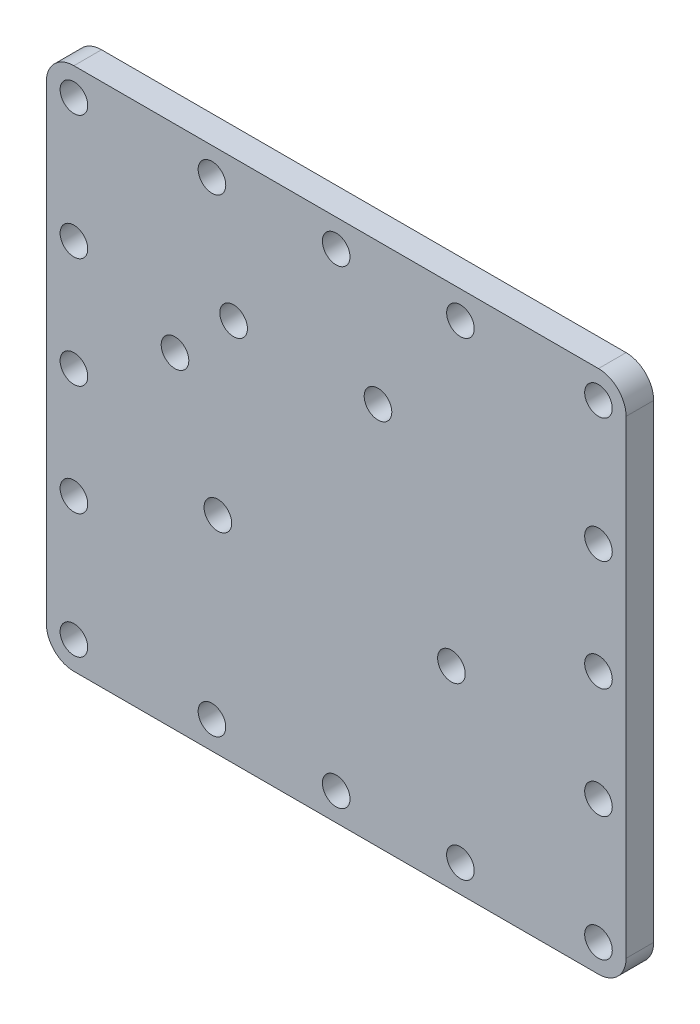
SolidWorks part; units mm, degrees
ref_plane "前视基准面" through (0, 0, 0) normal (0, 0, 1) x (1, 0, 0)
ref_plane "上视基准面" through (0, 0, 0) normal (0, 1, 0) x (1, 0, 0)
ref_plane "右视基准面" through (0, 0, 0) normal (1, 0, 0) x (0, 0, -1)
sketch "草图1" plane through (0, 0, 0) normal (0, 0, 1) x (1, 0, 0)
  line L0 (0, 41.5424) -> (0, -51.1772) construction
  line L1 (-95, -95) -> (95, -95)
  line L2 (-105, -85) -> (-105, 85)
  line L3 (-95, 95) -> (95, 95)
  line L4 (105, -85) -> (105, 85)
  line L5 (-105, -95) -> (105, 95) construction
  line L6 (-105, 95) -> (99.7638, -90.2625) construction
  line L7 (-39.3089, 0) -> (48.7848, 0) construction
  line L8 (95, 85) -> (95, -85) construction
  line L9 (-95, 85) -> (95, 85) construction
  circle A0 centre (-95, 85) radius 5
  circle A1 centre (95, 85) radius 5
  circle A2 centre (95, -85) radius 5
  circle A3 centre (-95, -85) radius 5
  arc A4 (95, 95) -> (105, 85) centre (95, 85) cw
  arc A5 (95, -95) -> (105, -85) centre (95, -85) ccw
  arc A6 (-95, -95) -> (-105, -85) centre (-95, -85) cw
  arc A7 (-105, 85) -> (-95, 95) centre (-95, 85) cw
  circle A8 centre (-37.156, 43.9209) radius 5
  circle A9 centre (15.1451, 43.9209) radius 5
  circle A10 centre (-58.3861, 23.2709) radius 5
  circle A11 centre (-42.8628, -19.9411) radius 5
  circle A12 centre (41.7332, -24.9411) radius 5
  circle A13 centre (95, 0) radius 5
  circle A14 centre (95, 40) radius 5
  circle A15 centre (95, -40) radius 5
  circle A16 centre (-95, -40) radius 5
  circle A17 centre (-95, 0) radius 5
  circle A18 centre (-95, 40) radius 5
  circle A19 centre (0, 85) radius 5
  circle A20 centre (-45, 85) radius 5
  circle A21 centre (45, 85) radius 5
  circle A22 centre (45, -85) radius 5
  circle A23 centre (0, -85) radius 5
  circle A24 centre (-45, -85) radius 5
  point P0 (0, 0)
  dimension "D2" = 10
  dimension "D3" = 10
  dimension "D4" = 10
  dimension "D6" = 10
  dimension "D7" = 10
  dimension "D8" = 10
  dimension "D9" = 10
  dimension "D10" = 10
  dimension "D11" = 10
  dimension "D12" = 10
  dimension "D13" = 10
  dimension "D14" = 40
  dimension "D15" = 40
  dimension "D16" = 10
  dimension "D17" = 10
  dimension "D18" = 45
  dimension "D19" = 45
  dimension "D1" = 190
  dimension "D5" = 210
extrude "凸台-拉伸1" add sketch "草图1" along normal mid plane 10
sketch "草图2" plane through (0, 0, -5) normal (0, 0, -1) x (-1, 0, 0)
  line L1 (-67.5, -62.5) -> (67.5, -62.5)
  line L2 (-67.5, -62.5) -> (-67.5, 62.5)
  line L3 (-67.5, 62.5) -> (67.5, 62.5)
  line L4 (67.5, -62.5) -> (67.5, 62.5)
  line L5 (-67.5, -62.5) -> (67.5, 62.5) construction
  line L6 (-67.5, 62.5) -> (67.5, -62.5) construction
  point P0 (0, 0)
  dimension "D1" = 135
  dimension "D2" = 125
extrude "切除-拉伸1" cut sketch "草图2" against normal blind 1
sketch "草图3" plane through (0, 0, -5) normal (0, 0, -1) x (-1, 0, 0)
  line L1 (-67.5, -65) -> (67.5, -65)
  line L2 (-72.5, -60) -> (-72.5, 60)
  line L3 (-67.5, 65) -> (67.5, 65)
  line L4 (72.5, -60) -> (72.5, 60)
  line L5 (-72.5, -65) -> (72.5, 65) construction
  line L6 (-72.5, 65) -> (72.5, -65) construction
  line L9 (-69.5, -67) -> (69.5, -67)
  line L10 (-74.5, -62) -> (-74.5, 62)
  line L11 (-69.5, 67) -> (69.5, 67)
  line L12 (74.5, -62) -> (74.5, 62)
  line L13 (-74.5, -67) -> (74.5, 67) construction
  line L14 (-74.5, 67) -> (74.5, -67) construction
  arc A0 (69.5, 67) -> (74.5, 62) centre (69.5, 62) cw
  arc A1 (67.5, 65) -> (72.5, 60) centre (67.5, 60) cw
  arc A2 (67.5, -65) -> (72.5, -60) centre (67.5, -60) ccw
  arc A3 (69.5, -67) -> (74.5, -62) centre (69.5, -62) ccw
  arc A4 (-69.5, -67) -> (-74.5, -62) centre (-69.5, -62) cw
  arc A5 (-67.5, -65) -> (-72.5, -60) centre (-67.5, -60) cw
  arc A6 (-74.5, 62) -> (-69.5, 67) centre (-69.5, 62) cw
  arc A7 (-72.5, 60) -> (-67.5, 65) centre (-67.5, 60) cw
  point P0 (0, 0)
  point P10 (0, 0)
  dimension "D5" = 5
  dimension "D1" = 145
  dimension "D2" = 130
  dimension "D3" = 2
  dimension "D4" = 2
extrude "切除-拉伸2" cut sketch "草图3" against normal blind 1.5
